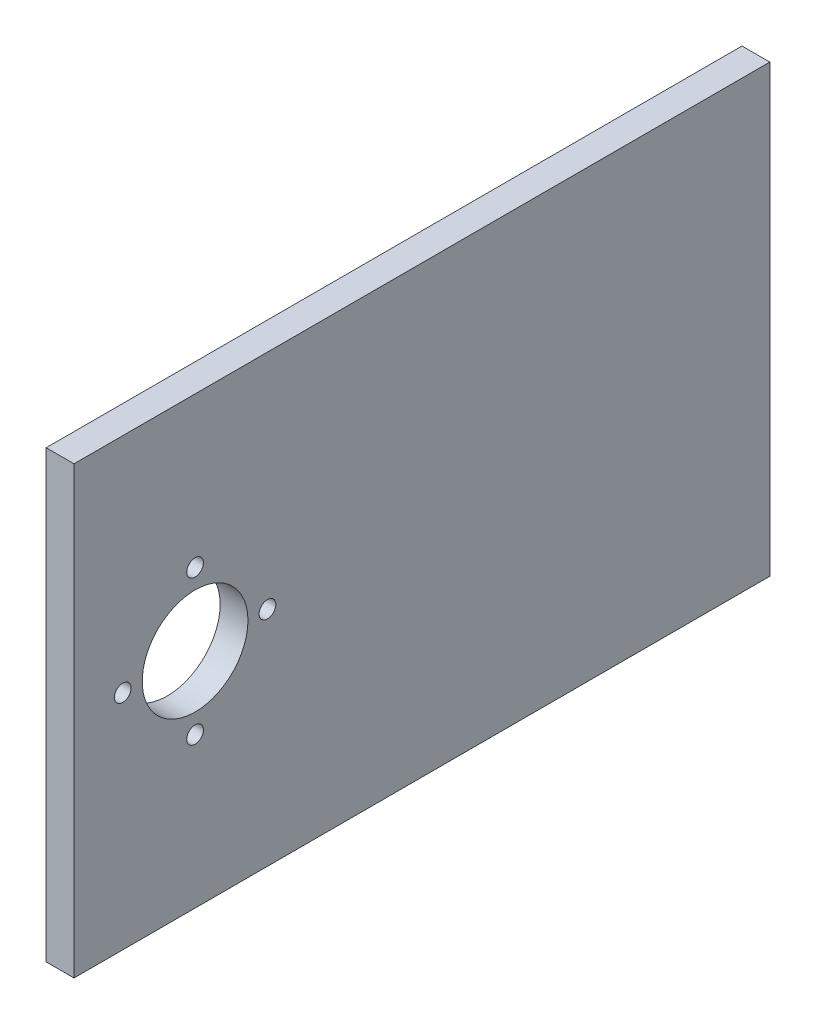
SolidWorks part; units mm, degrees
ref_plane "Front Plane" through (0, 0, 0) normal (1, 0, 0) x (0, 1, 0)
ref_plane "Top Plane" through (0, 0, 0) normal (0, 0, 1) x (0, 1, 0)
ref_plane "Right Plane" through (0, 0, 0) normal (0, 1, 0) x (-1, 0, 0)
sketch "Sketch1" plane through (0, 0, 0) normal (1, 0, 0) x (0, 1, 0)
  line L0 (-40, 40.75) -> (40, 40.75) construction
  line L1 (-40, -62.5) -> (40, -62.5)
  line L2 (-40, -62.5) -> (-40, 62.5)
  line L3 (-40, 62.5) -> (40, 62.5)
  line L4 (40, -62.5) -> (40, 62.5)
  line L5 (-40, -62.5) -> (40, 62.5) construction
  line L6 (-40, 62.5) -> (40, -62.5) construction
  line L7 (0, 62.5) -> (0, -62.5) construction
  circle A1 centre (0, 53.75) radius 1.5
  circle A2 centre (0, 27.75) radius 1.5
  circle A3 centre (-13, 40.75) radius 1.5
  circle A4 centre (13, 40.75) radius 1.5
  circle A5 centre (0, 40.75) radius 9.5
  point P0 (0, 0)
  dimension "D5" = 13
  dimension "D4" = 3
  dimension "D6" = 3
  dimension "D8" = 19
  dimension "D1" = 125
  dimension "D2" = 80
  dimension "D3" = 103.25
  dimension "D7" = 13
extrude "Boss-Extrude1" add sketch "Sketch1" along normal blind 5
